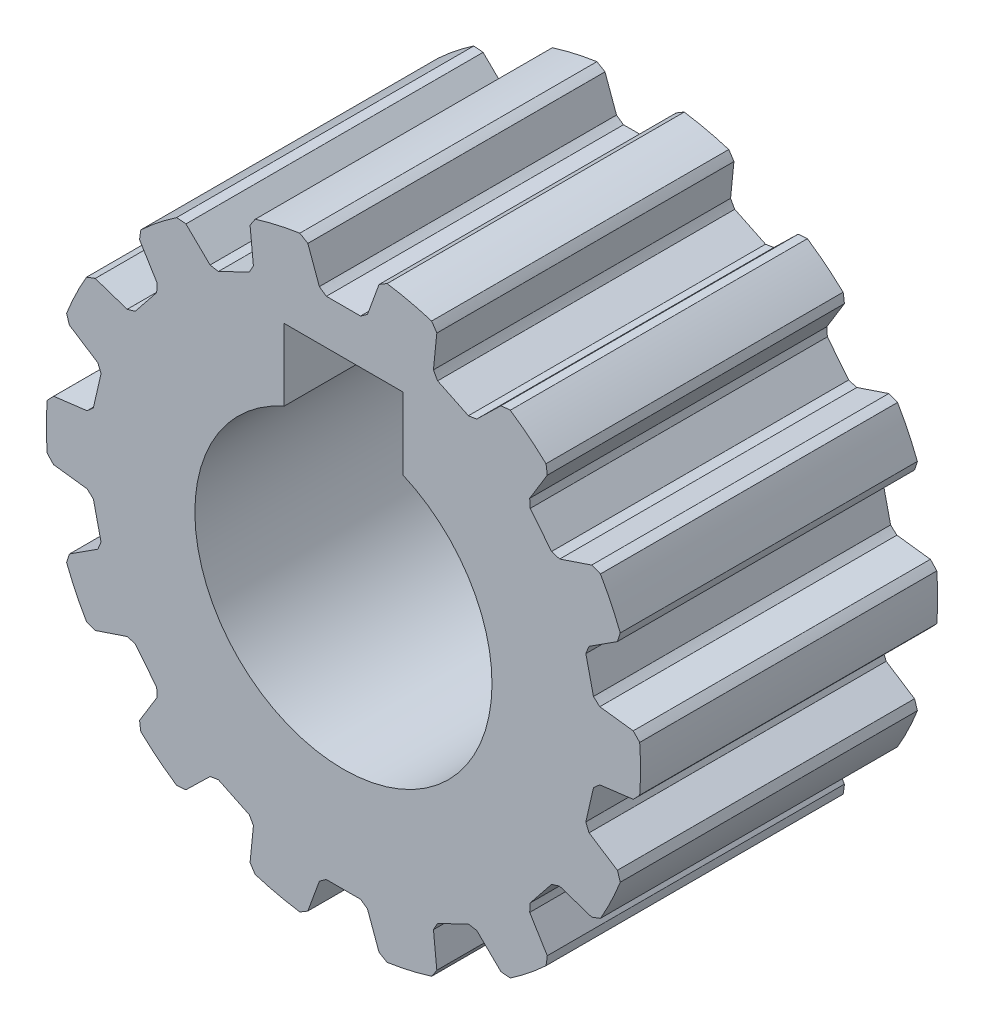
SolidWorks part; units mm, degrees
ref_plane "Front" through (0, 0, 0) normal (0, 0, 1) x (1, 0, 0)
ref_plane "Top" through (0, 0, 0) normal (0, 1, 0) x (1, 0, 0)
ref_plane "Right" through (0, 0, 0) normal (1, 0, 0) x (0, 0, -1)
sketch "Sketch1" plane through (0, 0, 0) normal (0, 0, 1) x (1, 0, 0)
  line L0 (0, 0) -> (0, 13.6162) construction
  line L2 (-2, 7) -> (2, 7)
  line L3 (-2, 7) -> (-2, 4.5826)
  line L5 (2, 7) -> (2, 4.5826)
  circle A0 centre (0, 0) radius 10
  arc A1 (-2, 4.5826) -> (2, 4.5826) centre (0, 0) ccw
  dimension "D1" = 20
  dimension "D2" = 10
  dimension "D3" = 4
  dimension "D4" = 7
extrude "Boss-Extrude1" add sketch "Sketch1" along normal blind 10
sketch "Sketch2" plane through (0, 0, 10) normal (0, 0, 1) x (1, 0, 0)
  line L0 (0, 0) -> (0, 16.7848) construction
  line L1 (-0.75, 8.5) -> (0.75, 8.5)
  line L2 (0.75, 8.5) -> (1.2666, 9.9195)
  line L3 (-0.75, 8.5) -> (-1.2666, 9.9195)
  circle A0 centre (0, 0) radius 10 construction
  point P5 (0, 0)
  point P10 (0.7166, 8.5239)
  dimension "D1" = 20
  dimension "D2" = 20
  dimension "D3" = 1.5
  dimension "D4" = 8.5
extrude "Cut-Extrude1" cut sketch "Sketch2" against normal blind 10 and the other way through all flip side to cut
pattern_circular "CirPattern1" count 14 over 360 about axis through (0, 0, 10) along (0, 0, -1) of "Cut-Extrude1"
fillet "Fillet1" radius 0.25 56 edges at (-4.3637, 7.3328, 5) (-3.0123, 7.9836, 5) (-3.1627, 9.4867, 5) (-1.2666, 9.9195, 5) (-0.75, 8.5, 5) (0.75, 8.5, 5) (1.2666, 9.9195, 5) (3.0123, 7.9836, 5) (4.3637, 7.3328, 5) (5.4451, 8.3875, 5) (6.9656, 7.175, 5) (6.178, 5.886, 5) (7.1132, 4.7133, 5) (8.5451, 5.1944, 5) (9.3889, 3.4422, 5) (8.12, 2.6226, 5) (8.4538, 1.1602, 5) (9.9526, 0.9724, 5) (9.9526, -0.9724, 5) (8.4538, -1.1602, 5) (8.12, -2.6226, 5) (9.3889, -3.4422, 5) (8.5451, -5.1944, 5) (7.1132, -4.7133, 5) (6.178, -5.886, 5) (6.9656, -7.175, 5) (5.4451, -8.3875, 5) (4.3637, -7.3328, 5) (3.0123, -7.9836, 5) (3.1627, -9.4867, 5) (1.2666, -9.9195, 5) (0.75, -8.5, 5) (-0.75, -8.5, 5) (-1.2666, -9.9195, 5) (-3.1627, -9.4867, 5) (-3.0123, -7.9836, 5) (-4.3637, -7.3328, 5) (-5.4451, -8.3875, 5) (-6.9656, -7.175, 5) (-6.178, -5.886, 5) (-7.1132, -4.7133, 5) (-8.5451, -5.1944, 5) (-9.3889, -3.4422, 5) (-8.12, -2.6226, 5) (-8.4538, -1.1602, 5) (-9.9526, -0.9724, 5) (-9.9526, 0.9724, 5) (-8.4538, 1.1602, 5) (-8.12, 2.6226, 5) (-9.3889, 3.4422, 5) (-8.5451, 5.1944, 5) (-7.1132, 4.7133, 5) (-6.178, 5.886, 5) (-6.9656, 7.175, 5) (-5.4451, 8.3875, 5) (3.1627, 9.4867, 5)
